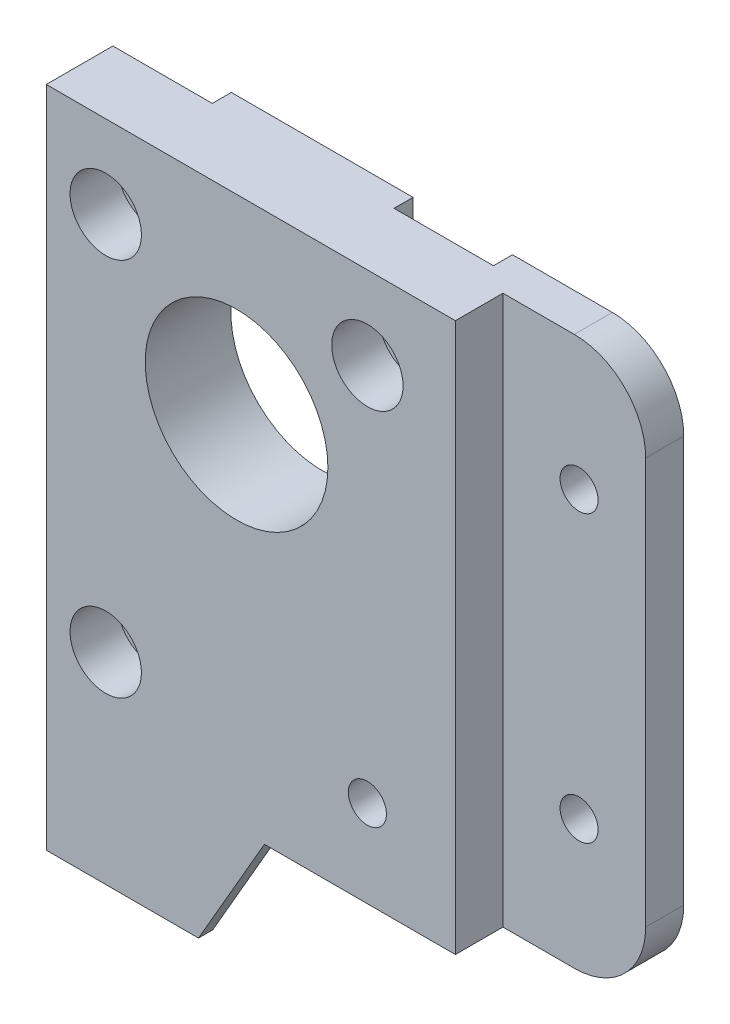
SolidWorks part; units mm, degrees
material "Custom Plastic"
ref_plane "Front Plane" through (0, 0, 0) normal (0, 0, 1) x (1, 0, 0)
ref_plane "Top Plane" through (0, 0, 0) normal (0, 1, 0) x (1, 0, 0)
ref_plane "Right Plane" through (0, 0, 0) normal (1, 0, 0) x (0, 0, -1)
sketch "Sketch1" plane through (0, 0, 0) normal (0, 0, 1) x (1, 0, 0)
  line L0 (-13.75, -19.7) -> (-9.788, -16.65) construction
  line L3 (20, 28.85) -> (38, 28.85)
  line L8 (20, -28.85) -> (-20, -28.85)
  line L9 (20, -28.85) -> (20, 28.85) construction
  line L10 (38, 28.85) -> (38, -28.85)
  line L11 (20, 28.85) -> (-20, 28.85)
  line L14 (-20, -28.85) -> (-20, 28.85)
  line L15 (20, -28.85) -> (-20, 28.85) construction
  line L16 (20, 28.85) -> (-20, -28.85) construction
  line L17 (-16.312, -16.3719) -> (-12.35, -13.3219)
  line L18 (-11.188, -23.0281) -> (-7.226, -19.9781)
  line L19 (0, -28.85) -> (0, 28.85) construction
  line L22 (38, -28.85) -> (20, -28.85)
  line L23 (17.2017, -17.3071) -> (20, -21.3437)
  line L24 (9.55, -19.7) -> (9.55, -28.85)
  line L25 (-9.55, 20.15) -> (-9.55, 28.85)
  line L26 (-17.2017, 17.7571) -> (-20, 21.7937)
  line L27 (9.55, 20.15) -> (9.55, 28.85)
  line L28 (17.2017, 17.7571) -> (20, 21.7937)
  line L29 (20, 21.7937) -> (20, 28.85)
  line L30 (-16.312, -16.3719) -> (-20, -16.3719)
  line L31 (20, -28.85) -> (20, -21.3437)
  line L32 (-20, -23.9) -> (-13.75, -23.9)
  circle A18 centre (-13.75, 20.15) radius 4.2
  circle A19 centre (13.75, 20.15) radius 4.2
  circle A20 centre (13.75, -19.7) radius 4.2
  arc A21 (-16.312, -16.3719) -> (-11.188, -23.0281) centre (-13.75, -19.7) ccw
  arc A22 (-7.226, -19.9781) -> (-12.35, -13.3219) centre (-9.788, -16.65) ccw
  circle A23 centre (0, 8.8) radius 9.6
  circle A24 centre (-5.725, -6.1) radius 4.2
  circle A25 centre (5.725, -6.1) radius 4.2
  point P0 (0, 0)
  point P14 (-6.4599, -14.088)
  point P31 (-11.769, -18.175)
  point P37 (5.725, -10.3)
  point P43 (20, 28.85)
  point P46 (-20, 28.85)
  dimension "D1" = 57.7
  dimension "D2" = 40
  dimension "D3" = 12.2
  dimension "D4" = 8.4
  dimension "D5" = 8.4
  dimension "D6" = 19.2
  dimension "D7" = 9.15
  dimension "D8" = 27.5
  dimension "D9" = 39.85
  dimension "D10" = 5
  dimension "D12" = 20.05
  dimension "D13" = 11.45
  dimension "D14" = 22.75
  dimension "D15" = 18
extrude "Boss-Extrude1" add sketch "Sketch1" along normal blind 2 contours L11 L14 L8 L9 A25 A24 A23 A22 L18 A21 L17 A20 A19 A18 region at (12.1005, -0.9425, 0)
sketch "Sketch4" plane through (0, 0, 2) normal (0, 0, 1) x (1, 0, 0)
  line L0 (0, -28.85) -> (0, 29) construction
  line L6 (38, -28.85) -> (20, -28.85) construction
  line L8 (-20, -28.85) -> (38, -28.85)
  line L11 (38, -28.85) -> (38, 28.85)
  line L12 (-20, 28.85) -> (-20, -28.85)
  line L13 (-20, -16.3719) -> (-20, 21.7937) construction
  line L14 (-20, 28.85) -> (38, 28.85)
  line L15 (20, 28.85) -> (38, 28.85) construction
  line L16 (38, 28.85) -> (38, -28.85) construction
  circle A2 centre (13.75, -19.7) radius 2
  circle A3 centre (-13.75, 20.15) radius 2
  circle A4 centre (13.75, 20.15) radius 2
  circle A10 centre (-13.75, -19.7) radius 2
  circle A11 centre (0, 8.8) radius 9.6
  circle A12 centre (0, 8.8) radius 9.6 construction
  dimension "D1" = 4
extrude "Boss-Extrude3" add sketch "Sketch4" along normal blind 2
sketch "Sketch5" plane through (0, 0, 4) normal (0, 0, 1) x (1, 0, 0)
  line L0 (-20, 0) -> (38, 0) construction
  line L3 (-20, 28.85) -> (-20, -28.85) construction
  line L4 (38, -28.85) -> (38, 28.85) construction
  circle A0 centre (31, 15) radius 2
  circle A1 centre (31, -15) radius 2
  dimension "D1" = 4
  dimension "D2" = 15
  dimension "D3" = 51
extrude "Cut-Extrude1" cut sketch "Sketch5" against normal blind 4
ref_plane "Plane1" through (0, 0, 0) normal (0, 0, -1) x (-1, 0, 0)
sketch "Sketch6" plane through (0, 0, 4) normal (0, 0, 1) x (1, 0, 0)
  line L0 (23, 28.85) -> (23, -28.85)
  line L1 (38, 28.85) -> (-20, 28.85) construction
  line L2 (-20, -28.85) -> (38, -28.85) construction
  line L3 (38, -28.85) -> (38, 28.85) construction
  circle A52 centre (-13.75, 20.15) radius 3.75
  circle A53 centre (13.75, 20.15) radius 3.75
  circle A54 centre (31, 15) radius 2
  circle A55 centre (13.75, -19.7) radius 3.75
  circle A56 centre (-13.75, -19.7) radius 3.75
  circle A57 centre (31, -15) radius 2
  circle A59 centre (31, 15) radius 2 construction
  circle A60 centre (31, -15) radius 2 construction
  line M5 (-20, 28.85) -> (-20, -28.85)
  line M6 (-20, -28.85) -> (38, -28.85)
  line M7 (38, -28.85) -> (38, 28.85)
  line M8 (38, 28.85) -> (-20, 28.85)
  circle M9 centre (13.75, -19.7) radius 2
  circle M11 centre (0, 8.8) radius 9.6
  dimension "D1" = 7.5
  dimension "D2" = 15
extrude "Boss-Extrude4" add sketch "Sketch6" along normal blind 5 contours A57 A56 A55 A54 A53 A52 M8 M5 M6 M7 M11 | A55 M9 region at (1.8471, -1.2843, 4) region at (10.1061, -19.7, 4)
sketch "Sketch7" plane through (0, 0, 4) normal (0, 0, 1) x (1, 0, 0)
  line L0 (38, -28.85) -> (38, 28.85) construction
  line L1 (30.5, 28.85) -> (38, 28.85)
  line L2 (38, 28.85) -> (38, 21.35)
  line L3 (-20, 0) -> (38, 0) construction
  line L4 (-20, 28.85) -> (-20, -28.85) construction
  line L5 (38, -28.85) -> (38, -21.35)
  line L6 (30.5, -28.85) -> (38, -28.85)
  arc A0 (38, 21.35) -> (30.5, 28.85) centre (30.5, 21.35) ccw
  arc A1 (38, -21.35) -> (30.5, -28.85) centre (30.5, -21.35) cw
  dimension "D1" = 15
extrude "Cut-Extrude2" cut sketch "Sketch7" against normal through all
sketch "Sketch9" plane through (-20, 0, 0) normal (-1, 0, 0) x (0, 0, 1)
  line L0 (9, -28.85) -> (9, -40.85)
  line L2 (9, -40.85) -> (0, -40.85)
  line L3 (0, -40.85) -> (0, -35.15)
  line L4 (0, -35.15) -> (3, -35.15)
  line L5 (3, -35.15) -> (3, -28.85)
  line L6 (9, -28.85) -> (0, -28.85) construction
  line L7 (0, -28.85) -> (0, -23.9) construction
  line L9 (3, -28.85) -> (9, -28.85)
  dimension "D1" = 6
  dimension "D2" = 12
  dimension "D3" = 6.3
extrude "Boss-Extrude5" add sketch "Sketch9" against normal blind 6
sketch "Sketch10" plane through (0, 0, 9) normal (0, 0, 1) x (1, 0, 0)
  line L0 (-14, -40.85) -> (-4, -40.85)
  line L1 (-4, -40.85) -> (2.9282, -28.85)
  line L3 (2.9282, -28.85) -> (-14, -28.85)
  line L4 (-14, -28.85) -> (-14, -40.85)
  dimension "D1" = 10
  dimension "D2" = 120
extrude "Boss-Extrude6" add sketch "Sketch10" against normal blind 1.5
